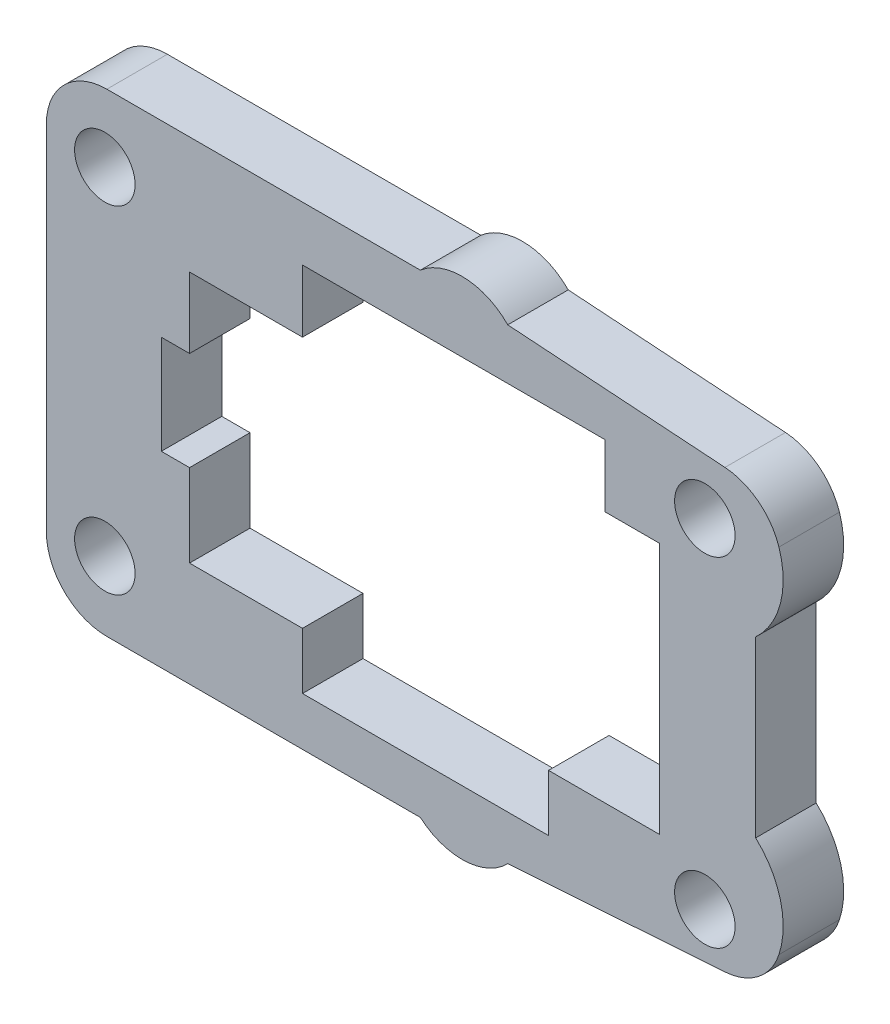
SolidWorks part; units mm, degrees
ref_plane "Plan de face" through (0, 0, 0) normal (0, 0, 1) x (1, 0, 0)
ref_plane "Plan de dessus" through (0, 0, 0) normal (0, 1, 0) x (1, 0, 0)
ref_plane "Plan de droite" through (0, 0, 0) normal (1, 0, 0) x (0, 0, -1)
sketch "Esquisse1" plane through (0, 0, 0) normal (0, 0, 1) x (1, 0, 0)
  line L0 (1211.1005, 2183.5097) -> (1246.1005, 2183.5328) construction
  line L1 (1210.9549, 2192.0629) -> (1210.9549, 2174.5629)
  line L2 (1213.9549, 2195.0629) -> (1229.4989, 2195.0629)
  line L3 (1235.6409, 2171.5629) -> (1210.9549, 2171.5629) construction
  line L4 (1244.6026, 2194.1457) -> (1233.8305, 2194.8823)
  line L5 (1210.9549, 2183.3129) -> (1246.1242, 2183.3129) construction
  line L6 (1246.1242, 2187.6282) -> (1246.1242, 2178.9976)
  line L7 (1244.6026, 2172.4801) -> (1233.8305, 2171.7435)
  line L8 (1213.9549, 2171.5629) -> (1229.4989, 2171.5629)
  line L9 (1241.3549, 2189.2629) -> (1241.3549, 2176.7629)
  line L10 (1241.3549, 2189.2629) -> (1238.6549, 2189.2629)
  line L11 (1238.6549, 2189.2629) -> (1238.6549, 2192.3629)
  line L12 (1238.6549, 2192.3629) -> (1223.6549, 2192.3629)
  line L13 (1223.6549, 2192.3629) -> (1223.6549, 2189.2629)
  line L14 (1223.6549, 2189.2629) -> (1218.0549, 2189.2629)
  line L15 (1218.0549, 2189.2629) -> (1218.0549, 2185.7629)
  line L16 (1218.0549, 2185.7629) -> (1216.6549, 2185.7629)
  line L17 (1216.6549, 2185.7629) -> (1216.6549, 2180.8629)
  line L18 (1216.6549, 2180.8629) -> (1218.0549, 2180.8629)
  line L19 (1218.0549, 2180.8629) -> (1218.0549, 2176.7629)
  line L20 (1218.0549, 2176.7629) -> (1223.6549, 2176.7629)
  line L21 (1223.6549, 2176.7629) -> (1223.6549, 2173.9629)
  line L22 (1223.6549, 2173.9629) -> (1235.8549, 2173.9629)
  line L23 (1235.8549, 2173.9629) -> (1235.8549, 2176.7629)
  line L24 (1235.8549, 2176.7629) -> (1241.3549, 2176.7629)
  line L25 (1243.6049, 2191.4581) -> (1243.6049, 2174.6705) construction
  arc A0 (1229.4989, 2195.0629) -> (1233.8305, 2194.8823) centre (1231.5684, 2192.6629) cw
  arc A1 (1244.6026, 2194.1457) -> (1247.2781, 2192.0631) centre (1244.3957, 2191.1202) cw
  arc A2 (1247.2781, 2192.0631) -> (1246.1242, 2187.6282) centre (1243.2469, 2190.7443) cw
  arc A3 (1247.2781, 2174.5627) -> (1246.1242, 2178.9976) centre (1243.2469, 2175.8815) ccw
  arc A4 (1244.6026, 2172.4801) -> (1247.2781, 2174.5627) centre (1244.3957, 2175.5056) ccw
  arc A5 (1229.4989, 2171.5629) -> (1233.8305, 2171.7435) centre (1231.5684, 2173.9629) ccw
  circle A6 centre (1243.6049, 2191.4581) radius 1.5
  circle A7 centre (1213.8549, 2191.6629) radius 1.5
  circle A8 centre (1213.8549, 2174.9629) radius 1.5
  circle A9 centre (1243.6049, 2174.6705) radius 1.5
  arc A10 (1213.9549, 2171.5629) -> (1210.9549, 2174.5629) centre (1213.9549, 2174.5629) cw
  arc A11 (1213.9549, 2195.0629) -> (1210.9549, 2192.0629) centre (1213.9549, 2192.0629) ccw
  point P53 (1210.9549, 2195.0629)
  point P54 (1231.7004, 2170.7966)
  point P55 (1231.7004, 2195.8292)
  dimension "D5" = 3
  dimension "D6" = 3
  dimension "D7" = 3
  dimension "D8" = 3
  dimension "D12" = 1.9
  dimension "D29" = 3
  dimension "D30" = 3.45
  dimension "D1" = 35
  dimension "D2" = 23.5
  dimension "D3" = 2195.0629
  dimension "D4" = 1210.9549
  dimension "D9" = 1.4
  dimension "D10" = 1.9
  dimension "D11" = 1.4
  dimension "D13" = 24.7
  dimension "D14" = 4.9
  dimension "D15" = 2.45
  dimension "D16" = 1.4
  dimension "D17" = 1.4
  dimension "D18" = 5.7
  dimension "D19" = 2.7
  dimension "D20" = 12.7
  dimension "D21" = 5.8
  dimension "D22" = 15
  dimension "D23" = 5.8
  dimension "D24" = 12.5
  dimension "D25" = 12.5
  dimension "D26" = 12.7
  dimension "D27" = 2.4
  dimension "D28" = 12.2
  dimension "D31" = 25.0326
base flange "Tôle de base pliée1" sketch "Esquisse1" thickness 3 reverse thickness direction no parameters "D1"=1.5
sketch "Lignes de pliage1" [suppressed] plane through (0, 0, 0) normal (0, 1, 0) x (1, 0, 0)
sketch "Cube de visualisation1" [suppressed] plane through (0, 0, 0) normal (0, 1, 0) x (1, 0, 0)
sheet metal parameters "Tôlerie1" thickness 3 parameters "D1"=1.5
flat pattern "Etat déplié1" [suppressed]
sketch "Lignes de pliage2" plane through (0, 0, 0) normal (0, 1, 0) x (1, 0, 0)
sketch3d "Cube de visualisation2" [suppressed]
  line L0 (-20.6135, -21.8688, 0) -> (15.9199, -21.8688, 0) construction
  line L1 (-20.6135, 3.169, 0) -> (15.9199, 3.169, 0) construction
  line L2 (-20.6135, -21.8688, 0) -> (-20.6135, 3.169, 0) construction
  line L3 (15.9199, -21.8688, 0) -> (15.9199, 3.169, 0) construction
